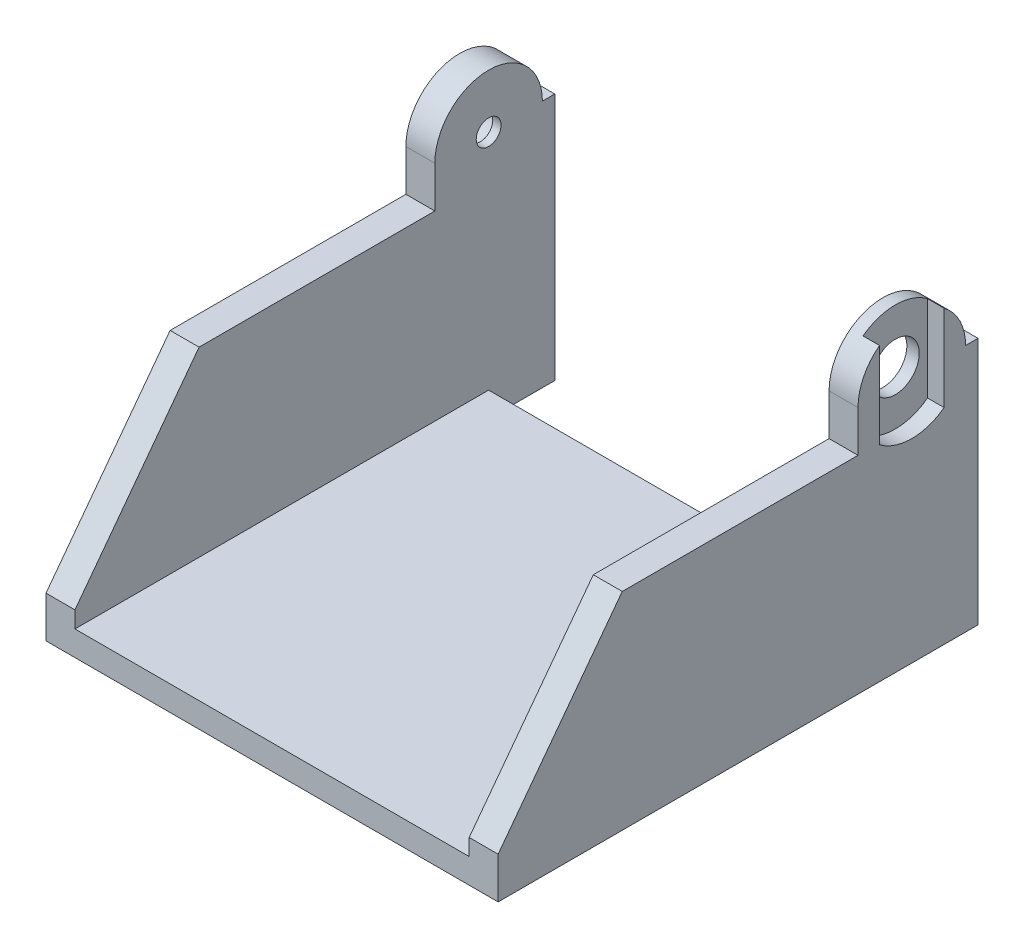
SolidWorks part; units mm, degrees
ref_plane "Front Plane" through (0, 0, 0) normal (0, 0, 1) x (1, 0, 0)
ref_plane "Top Plane" through (0, 0, 0) normal (0, 1, 0) x (1, 0, 0)
ref_plane "Right Plane" through (0, 0, 0) normal (1, 0, 0) x (0, 0, -1)
sketch "Sketch1" plane through (0, 0, 0) normal (0, 0, 1) x (1, 0, 0)
  line L0 (0, 0) -> (-23.825, 0) construction
  line L2 (-23.825, 0) -> (-27.325, 0)
  line L3 (-23.825, 0) -> (-23.825, -30)
  line L4 (-23.825, -30) -> (-27.325, -30)
  line L5 (-27.325, 0) -> (-27.325, -30)
  line L6 (-23.825, -30) -> (0, -30)
  line L7 (-23.825, -30) -> (-23.825, -27)
  line L8 (-23.825, -27) -> (0, -27)
  line L9 (0, -30) -> (0, -27)
  dimension "D1" = 23.825
  dimension "D2" = 3.5
  dimension "D3" = 30
  dimension "D4" = 3
extrude "Boss-Extrude1" add sketch "Sketch1" along normal blind 50 contours L2 L5 L4 L3 | L6 L9 L8 L3 region at (-25.575, -15, 0) region at (-11.9125, -28.5, 0)
sketch "Sketch2" plane through (-23.825, 0, 0) normal (1, 0, 0) x (0, 0, -1)
  line L1 (0, 0) -> (8, 0)
  line L2 (0, 0) -> (0, -30)
  line L3 (0, -30) -> (8, -30)
  line L4 (8, 0) -> (8, -30)
  circle A0 centre (0, 0) radius 1.5
  circle A1 centre (0, 0) radius 6.5
  line M1 (0, -27) -> (0, 0)
  line M2 (0, 0) -> (-50, 0)
  dimension "D1" = 3
  dimension "D2" = 13
  dimension "D3" = 8
extrude "Boss-Extrude2" add sketch "Sketch2" against normal blind 3.5 contours A1 L2 L3 L4 L1 M1 | L2 A1 L1 A0 | L1 A1 A0 M2 region at (-23.825, 2.8781, 0) region at (-23.825, -2.8781, -2.8781) region at (-23.825, -16.9641, -4.1992)
sketch "Sketch3" plane through (-27.325, 0, 0) normal (-1, 0, 0) x (0, 0, 1)
  circle A0 centre (0, 0) radius 1.5
extrude "Cut-Extrude1" cut sketch "Sketch3" against normal through all both and the other way through all
mirror "Mirror1" about plane through (0, 0, 50) normal (-1, 0, 0) of "Cut-Extrude1", "Boss-Extrude2", "Boss-Extrude1"
sketch "Sketch4" plane through (-27.325, 0, 0) normal (-1, 0, 0) x (0, 0, 1)
  circle A0 centre (0, 0) radius 2.5
  dimension "D1" = 5
extrude "Cut-Extrude2" cut sketch "Sketch4" against normal blind 3.15 and the other way through all
sketch "Sketch5" plane through (27.325, 0, 0) normal (1, 0, 0) x (0, 0, -1)
  circle A0 centre (0, 0) radius 2.9
  dimension "D1" = 5.8
extrude "Cut-Extrude3" cut sketch "Sketch5" against normal blind 7.15
sketch "Sketch6" plane through (-27.325, 0, 0) normal (-1, 0, 0) x (0, 0, 1)
  line L1 (50, 0) -> (25, 0)
  line L2 (50, 0) -> (50, -25)
  line L5 (35, -5) -> (50, -25)
  line L7 (6.5, 0) -> (50, 0)
  line L8 (6.5, 0) -> (6.5, -5)
  line L9 (6.5, -5) -> (35, -5)
  line L10 (50, 0) -> (50, -10)
  line M4 (50, 0) -> (6.5, 0)
  line M9 (50, -30) -> (50, 0)
  dimension "D1" = 5
  dimension "D2" = 25
  dimension "D3" = 5
extrude "Cut-Extrude4" cut sketch "Sketch6" against normal blind 7.15 contours L5 M4 M9 region at (-27.325, -5, 49.4983)
ref_plane "Plane1" through (0, 0, 0) normal (1, 0, 0) x (0, 0, -1)
mirror "Mirror2" about plane through (0, 0, 0) normal (1, 0, 0) of "Cut-Extrude4"
sketch "Sketch7" plane through (-24.175, 0, 0) normal (-1, 0, 0) x (0, 0, 1)
  circle A0 centre (0, 0) radius 1.5
  circle A1 centre (0, 0) radius 2.5
extrude "Boss-Extrude3" add sketch "Sketch7" along normal blind 0.65
sketch "Sketch8" plane through (27.325, 0, 0) normal (1, 0, 0) x (0, 0, -1)
  line L1 (-2.9, 0) -> (2.9, 0)
  line L2 (-2.9, 0) -> (-2.9, 7)
  line L3 (-2.9, 7) -> (2.9, 7)
  line L4 (2.9, 0) -> (2.9, 7)
  line L5 (-2.9, 0) -> (2.9, 0)
  line L6 (-2.9, 0) -> (-2.9, -5)
  line L7 (-2.9, -5) -> (2.9, -5)
  line L8 (2.9, 0) -> (2.9, -5)
  line L9 (-3.9, 8) -> (3.9, 8)
  line L10 (-3.9, 8) -> (-3.9, -6)
  line L11 (-3.9, -6) -> (3.9, -6)
  line L12 (3.9, 8) -> (3.9, -6)
  circle A0 centre (0, 0) radius 6.5
  circle A1 centre (0, 0) radius 2.9
  circle M4 centre (0, 0) radius 2.9
  arc M5 (6.5, 0) -> (-6.5, 0) centre (0, 0) ccw
  dimension "D1" = 5
  dimension "D2" = 7
  dimension "D3" = 5.8
  dimension "D4" = 1
  dimension "D5" = 1
  dimension "D6" = 1
  dimension "D7" = 1
extrude "Cut-Extrude6" cut sketch "Sketch8" against normal blind 2 contours L10 A0 L11 L12 L4 L8 L7 L6 L2 M5 | L4 L2 M4 M5 | L8 L6 L7 M4 | L11 A0 region at (27.325, -2.5, 3.0416) region at (27.325, -3.5619, 0) region at (27.325, 4.2303, 0) region at (27.325, -6.2007, 0)
